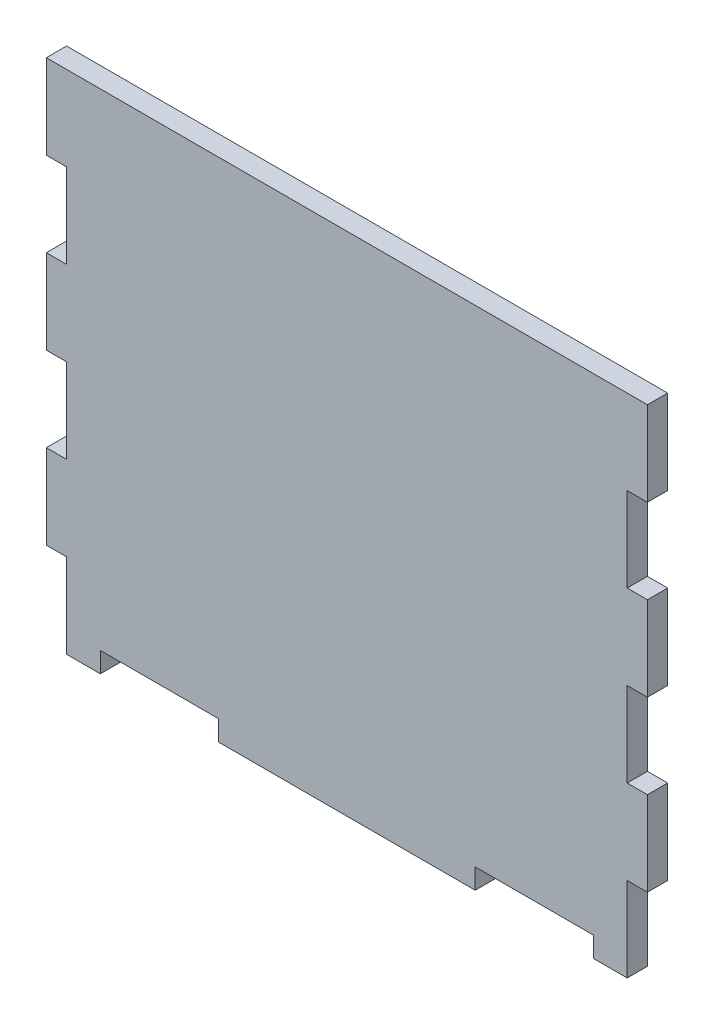
SolidWorks part; units mm, degrees
ref_plane "Front" through (0, 0, 0) normal (0, 0, 1) x (1, 0, 0)
ref_plane "Top" through (0, 0, 0) normal (0, 1, 0) x (1, 0, 0)
ref_plane "Right" through (0, 0, 0) normal (1, 0, 0) x (0, 0, -1)
sketch "Sketch1" plane through (0, 0, 0) normal (0, 0, 1) x (1, 0, 0)
  line L1 (0, 0) -> (-178, 0)
  line L2 (0, 0) -> (0, 150)
  line L3 (0, 150) -> (-178, 150)
  line L4 (-178, 0) -> (-178, 150)
  dimension "D1" = 150
  dimension "D2" = 178
extrude "Boss-Extrude1" add sketch "Sketch1" along normal blind 6
sketch "Sketch2" plane through (0, 0, 6) normal (0, 0, 1) x (1, 0, 0)
  line L0 (-178, 150) -> (-178, 0) construction
  line L1 (-178, 125) -> (-172, 125)
  line L2 (-178, 125) -> (-178, 100)
  line L3 (-178, 100) -> (-172, 100)
  line L4 (-172, 125) -> (-172, 100)
  line L5 (0, 150) -> (-178, 150) construction
  dimension "D1" = 25
  dimension "D2" = 25
  dimension "D3" = 6
extrude "Cut-Extrude1" cut sketch "Sketch2" against normal blind 6
pattern_linear "LPattern1" count 3 spacing 50 along (0, -1, 0) count 2 spacing 172 along (1, 0, 0) of "Cut-Extrude1"
sketch "Sketch3" plane through (0, 0, 6) normal (0, 0, 1) x (1, 0, 0)
  line L0 (-172, 0) -> (-6, 0) construction
  line L1 (-16, 0) -> (-51, 0)
  line L2 (-16, 0) -> (-16, 6)
  line L3 (-16, 6) -> (-51, 6)
  line L4 (-51, 0) -> (-51, 6)
  line L5 (-89, 150) -> (-89, 0) construction
  line L6 (-6, 25) -> (-6, 0) construction
  line L7 (0, 150) -> (-178, 150) construction
  line L8 (-127, 0) -> (-127, 6)
  line L9 (-162, 6) -> (-127, 6)
  line L10 (-162, 0) -> (-162, 6)
  line L11 (-162, 0) -> (-127, 0)
  dimension "D1" = 35
  dimension "D2" = 10
  dimension "D3" = 6
extrude "Cut-Extrude2" cut sketch "Sketch3" against normal through all
